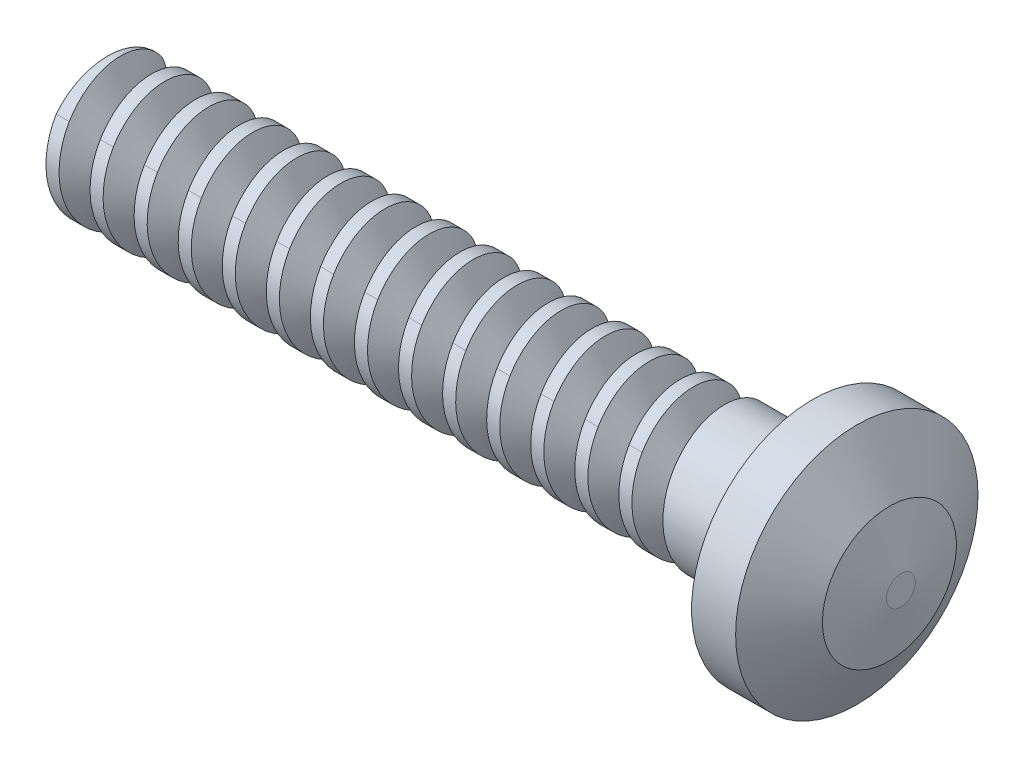
SolidWorks part; units mm, degrees
ref_plane "前视基准面" through (0, 0, 0) normal (0, 0, 1) x (1, 0, 0)
ref_plane "上视基准面" through (0, 0, 0) normal (0, 1, 0) x (1, 0, 0)
ref_plane "右视基准面" through (0, 0, 0) normal (1, 0, 0) x (0, 0, -1)
sketch "草图1" plane through (0, 0, 0) normal (1, 0, 0) x (0, 0, -1)
  circle A0 centre (0, 0) radius 1.5
  dimension "D1" = 3
extrude "凸台-拉伸1" add sketch "草图1" along normal blind 16
sketch "草图2" plane through (16, 0, 0) normal (1, 0, 0) x (0, 0, -1)
  circle A0 centre (0, 0) radius 2.75
  dimension "D1" = 5.5
extrude "凸台-拉伸2" add sketch "草图2" along normal blind 2
sketch "草图3" plane through (0, 0, 0) normal (0, 1, 0) x (1, 0, 0)
  line L9 (16, -2.75) -> (18, -2.75) construction
  line L10 (17, -2.75) -> (18, -2.75)
  line L11 (17, -2.75) -> (17.7398, -1.5199)
  line L12 (17.7398, -1.5199) -> (18, -0.3278)
  line L13 (18, -2.75) -> (18, 2.75) construction
  line L14 (18, -0.3278) -> (18, -2.75)
revolve "切除-旋转7" cut sketch "草图3" angle 360 about axis through (16, 0, 0) along (-1, 0, 0)
sketch "草图4" plane through (0, 0, 0) normal (0, 0, 1) x (1, 0, 0)
  line L0 (0, -1.5) -> (-0.3448, -1.5)
  line L1 (-0.3448, -1.5) -> (0, -0.9242)
  line L2 (0, 1.5) -> (0, -1.5) construction
  line L3 (0, -0.9242) -> (0.3586, -1.5)
  line L4 (0, -1.5) -> (16, -1.5) construction
  line L5 (0.3586, -1.5) -> (0, -1.5)
sketch "草图5" plane through (0, 0, 0) normal (-1, 0, 0) x (0, 0, 1)
  circle A0 centre (0, 0) radius 1.5
curve "螺旋线/涡状线1" pitch 1 height 15 turns 15
sweep "切除-扫描1" cut profiles "草图4" path "螺旋线/涡状线1"
